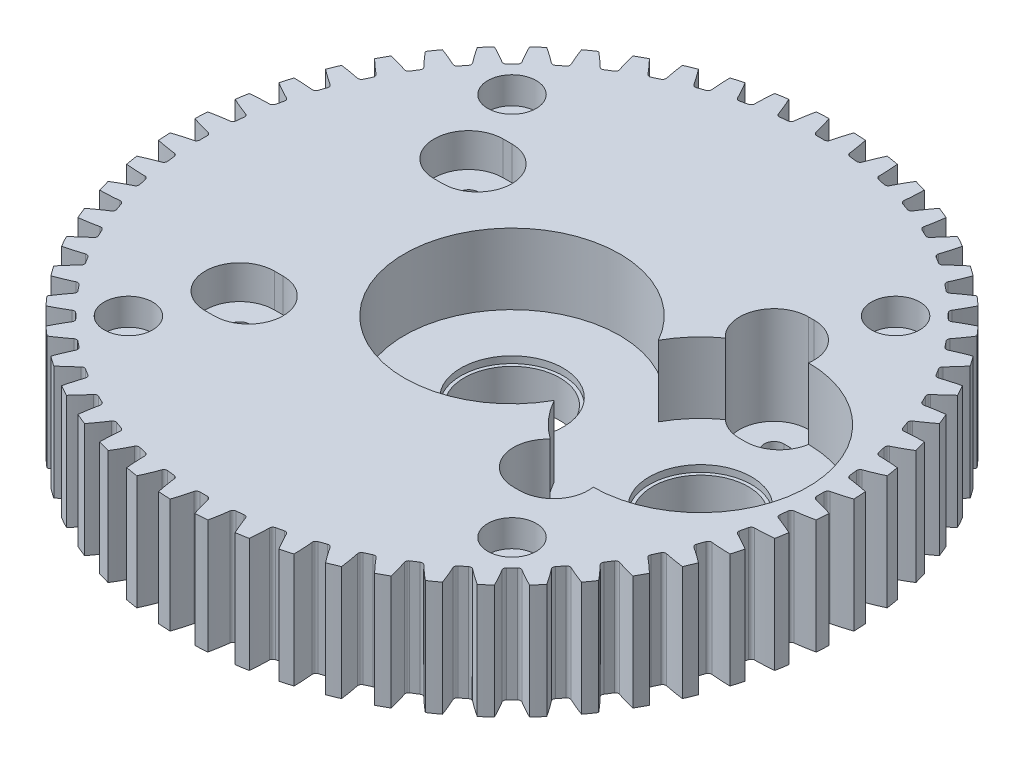
SolidWorks part; units mm, degrees
note: The reader was unsure of these and kept them because the rebuilt part matched: shared geometry of "Sketch10<3>".
ref_plane "Front Plane" through (0, 0, 0) normal (0, 0, 1) x (1, 0, 0)
ref_plane "Top Plane" through (0, 0, 0) normal (0, 1, 0) x (1, 0, 0)
ref_plane "Right Plane" through (0, 0, 0) normal (1, 0, 0) x (0, 0, -1)
sketch "Sketch1" plane through (0, 0, 0) normal (0, 1, 0) x (1, 0, 0)
  line L1 (-28.5, 28.5) -> (28.5, 28.5) construction
  line L2 (-28.5, 28.5) -> (-28.5, -28.5) construction
  line L3 (-28.5, -28.5) -> (28.5, -28.5) construction
  line L4 (28.5, 28.5) -> (28.5, -28.5) construction
  line L5 (-28.5, 28.5) -> (28.5, -28.5) construction
  line L6 (-28.5, -28.5) -> (28.5, 28.5) construction
  circle A0 centre (0, 0) radius 49
  circle A1 centre (-28.5, 28.5) radius 2.1
  circle A2 centre (28.5, 28.5) radius 2.1
  circle A3 centre (28.5, -28.5) radius 2.1
  circle A4 centre (-28.5, -28.5) radius 2.1
  dimension "D1" = 98
  dimension "D3" = 4.2
  dimension "D2" = 57
extrude "Boss-Extrude1" add sketch "Sketch1" along normal blind 17
sketch "Sketch5" plane through (0, 17, 0) normal (0, 1, 0) x (1, 0, 0)
  line L0 (0, 0) -> (0, 59.2156) construction
  line L2 (-0.5598, 45.8381) -> (0.5598, 45.8381)
  line L3 (0.5598, 46.3381) -> (0.5598, 45.8381)
  arc A1 (1.0455, 46.2191) -> (1.8387, 48.9655) centre (35.0396, 37.8887) cw
  circle A6 centre (0, 0) radius 48
  circle A7 centre (0, 0) radius 45.8381
  arc A10 (-1.0455, 46.2191) -> (-1.8387, 48.9655) centre (-35.0396, 37.8887) ccw
  arc A11 (-1.8387, 48.9655) -> (1.8387, 48.9655) centre (0, 45.6487) cw
  arc A12 (-1.0455, 46.2191) -> (-0.5598, 45.8381) centre (-0.5598, 46.3381) ccw
  arc A13 (1.0455, 46.2191) -> (0.5598, 45.8381) centre (0.5598, 46.3381) cw
  circle A14 centre (0, 0) radius 49 construction
  point P6 (0, 45.8381)
  point P9 (0.5, 48)
  point P14 (0, 48)
  dimension "D3" = 0.5598
  dimension "D1" = 91.6763
  dimension "D2" = 96
  dimension "D4" = 35
  dimension "D5" = 0.5
  dimension "D6" = 0.5
  dimension "D7" = 1.8387
  dimension "D8" = 1.0455
extrude "Cut-Extrude1" cut sketch "Sketch5" against normal through all
pattern_circular "CirPattern1" count 56 over 360 about axis through (0, 0, 0) along (0, 1, 0) of "Cut-Extrude1"
sketch "Sketch6" plane through (0, 17, 0) normal (0, 1, 0) x (1, 0, 0)
  line L0 (0, 0) -> (28, 0)
  circle A0 centre (0, 0) radius 16
  circle A1 centre (28, 0) radius 16
  dimension "D2" = 32
  dimension "D3" = 32
  dimension "D1" = 28
extrude "Cut-Extrude2" cut sketch "Sketch6" against normal blind 10.5
sketch "Sketch7" plane through (0, 17, 0) normal (0, 1, 0) x (1, 0, 0)
  line L0 (0, 0) -> (28, 0)
  circle A0 centre (0, 0) radius 7.1
  circle A1 centre (28, 0) radius 7.1
  dimension "D1" = 14.2
  dimension "D3" = 14.2
  dimension "D2" = 28
extrude "Cut-Extrude3" cut sketch "Sketch7" against normal through all
sketch "Sketch8" plane through (0, 17, 0) normal (0, 1, 0) x (1, 0, 0)
  circle A0 centre (0, 0) radius 7.6
  circle A1 centre (28, 0) radius 7.6
  dimension "D1" = 15.2
  dimension "D2" = 15.2
extrude "Cut-Extrude4" cut sketch "Sketch8" against normal blind 11.5
sketch "Sketch9" plane through (0, 17, 0) normal (0, 1, 0) x (1, 0, 0)
  line L1 (-28, 0) -> (28, 0) construction
  line L3 (23, -16.785) -> (22.15, -16.785)
  line L6 (28, -16.785) -> (23, -16.785) construction
  line L7 (22.15, -18.235) -> (23, -18.235)
  line L10 (28, 0) -> (28, -16.785) construction
  line L11 (22.15, -15.335) -> (23, -15.335)
  line L13 (22.15, -18.235) -> (23, -18.235)
  line L14 (22.15, -15.335) -> (23, -15.335)
  line L15 (22.15, -18.235) -> (23, -18.235)
  line L16 (22.15, -15.335) -> (23, -15.335)
  line L17 (22.15, -18.235) -> (23, -18.235)
  line L18 (22.15, -15.335) -> (23, -15.335)
  line L19 (28, 16.785) -> (23, 16.785) construction
  line L20 (22.15, 15.335) -> (23, 15.335)
  line L21 (22.15, 18.235) -> (23, 18.235)
  line L22 (22.15, 15.335) -> (23, 15.335)
  line L23 (22.15, 18.235) -> (23, 18.235)
  line L24 (22.15, 15.335) -> (23, 15.335)
  line L25 (22.15, 18.235) -> (23, 18.235)
  line L26 (22.15, 15.335) -> (23, 15.335)
  line L27 (22.15, 18.235) -> (23, 18.235)
  line L28 (0, 0) -> (0, -29.297) construction
  line L29 (-22.15, -15.55) -> (-23.45, -15.55)
  line L30 (-22.15, -18.45) -> (-23.45, -18.45)
  line L31 (-28, -17) -> (-23.45, -17) construction
  line L32 (-22.15, -15.55) -> (-23.45, -15.55)
  line L33 (-22.15, -18.45) -> (-23.45, -18.45)
  line L34 (-22.15, -15.55) -> (-23.45, -15.55)
  line L35 (-22.15, -18.45) -> (-23.45, -18.45)
  line L36 (-22.15, -15.55) -> (-23.45, -15.55)
  line L37 (-22.15, -18.45) -> (-23.45, -18.45)
  line L40 (-22.15, -15.55) -> (-23.45, -15.55)
  line L41 (-22.15, -18.45) -> (-23.45, -18.45)
  line L42 (-22.15, -15.55) -> (-23.45, -15.55)
  line L43 (-22.15, -18.45) -> (-23.45, -18.45)
  line L44 (-22.15, -15.55) -> (-23.45, -15.55)
  line L45 (-22.15, -18.45) -> (-23.45, -18.45)
  line L46 (-22.15, -15.55) -> (-23.45, -15.55)
  line L47 (-22.15, -18.45) -> (-23.45, -18.45)
  line L48 (-23.45, -17) -> (-22.15, -17)
  line L49 (-28, 17) -> (-23.45, 17) construction
  line L50 (-23.45, 17) -> (-22.15, 17)
  line L51 (-22.15, 18.45) -> (-23.45, 18.45)
  line L52 (-22.15, 15.55) -> (-23.45, 15.55)
  line L53 (-22.15, 18.45) -> (-23.45, 18.45)
  line L54 (-22.15, 15.55) -> (-23.45, 15.55)
  line L55 (-22.15, 18.45) -> (-23.45, 18.45)
  line L56 (-22.15, 15.55) -> (-23.45, 15.55)
  line L57 (-22.15, 18.45) -> (-23.45, 18.45)
  line L58 (-22.15, 15.55) -> (-23.45, 15.55)
  line L59 (-22.15, 18.45) -> (-23.45, 18.45)
  line L60 (-22.15, 15.55) -> (-23.45, 15.55)
  line L61 (-22.15, 18.45) -> (-23.45, 18.45)
  line L62 (-22.15, 15.55) -> (-23.45, 15.55)
  line L63 (-22.15, 18.45) -> (-23.45, 18.45)
  line L64 (-22.15, 15.55) -> (-23.45, 15.55)
  line L65 (-22.15, 18.45) -> (-23.45, 18.45)
  line L66 (-22.15, 15.55) -> (-23.45, 15.55)
  arc A8 (23, -18.235) -> (23, -15.335) centre (23, -16.785) ccw
  arc A9 (22.15, -15.335) -> (22.15, -18.235) centre (22.15, -16.785) ccw
  arc A10 (22.15, 15.335) -> (22.15, 18.235) centre (22.15, 16.785) cw
  arc A11 (23, 18.235) -> (23, 15.335) centre (23, 16.785) cw
  arc A14 (-22.15, -15.55) -> (-22.15, -18.45) centre (-22.15, -17) cw
  arc A15 (-23.45, -18.45) -> (-23.45, -15.55) centre (-23.45, -17) cw
  arc A16 (-23.45, 18.45) -> (-23.45, 15.55) centre (-23.45, 17) ccw
  arc A17 (-22.15, 15.55) -> (-22.15, 18.45) centre (-22.15, 17) ccw
  point P5 (28, 0)
  point P30 (0, 0)
  point P40 (-28, 0)
  point P43 (-28, 0)
  dimension "D2" = 2.9
  dimension "D4" = 2.9
  dimension "D6" = 1.45
  dimension "D1" = 5
  dimension "D3" = 5.85
  dimension "D5" = 1.3
  dimension "D7" = 28
extrude "Cut-Extrude5" cut sketch "Sketch9" against normal through all
sketch "Sketch10" plane through (0, 17, 0) normal (0, 1, 0) x (1, 0, 0)
  line L0 (22.15, -11.66) -> (23, -11.66)
  line L1 (22.15, -21.91) -> (23, -21.91)
  line L2 (0, 0) -> (28, 0) construction
  line L3 (22.15, 21.91) -> (23, 21.91)
  line L4 (22.15, 11.66) -> (23, 11.66)
  line L5 (-23.45, -11.875) -> (-22.15, -11.875)
  line L6 (-23.45, -22.125) -> (-22.15, -22.125)
  line L7 (-23.45, 22.125) -> (-22.15, 22.125)
  line L8 (-23.45, 11.875) -> (-22.15, 11.875)
  arc A2 (23, -21.91) -> (23, -11.66) centre (23, -16.785) ccw
  arc A3 (22.15, -11.66) -> (22.15, -21.91) centre (22.15, -16.785) ccw
  arc A4 (22.15, 11.66) -> (22.15, 21.91) centre (22.15, 16.785) cw
  arc A5 (23, 21.91) -> (23, 11.66) centre (23, 16.785) cw
  arc A6 (-23.45, -11.875) -> (-23.45, -22.125) centre (-23.45, -17) ccw
  arc A7 (-22.15, -22.125) -> (-22.15, -11.875) centre (-22.15, -17) ccw
  arc A8 (-22.15, 22.125) -> (-22.15, 11.875) centre (-22.15, 17) cw
  arc A9 (-23.45, 11.875) -> (-23.45, 22.125) centre (-23.45, 17) cw
  dimension "D1" = 10.25
  dimension "D2" = 10.25
  dimension "D3" = 10.25
extrude "Cut-Extrude6" cut sketch "Sketch10" against normal blind 14.5 contours A5 L3 A4 L4 | L0 A3 L1 A2
sketch "Sketch11" plane through (0, 17, 0) normal (0, 1, 0) x (1, 0, 0)
  circle A0 centre (-28.5, -28.5) radius 3.6
  circle A1 centre (-28.5, 28.5) radius 3.6
  circle A2 centre (28.5, 28.5) radius 3.6
  circle A3 centre (28.5, -28.5) radius 3.6
  dimension "D1" = 7.2
extrude "Cut-Extrude7" cut sketch "Sketch11" against normal blind 4
extrude "Cut-Extrude8" cut sketch "Sketch10<3>" against normal blind 5 contours A9 L8 A8 L7 | L6 A7 L5 A6
sketch "Sketch10<3>" plane through (0, 17, 0) normal (0, 1, 0) x (1, 0, 0) same geometry as "Sketch10"
sketch "Sketch12" plane through (0, 17, 0) normal (0, 1, 0) x (1, 0, 0)
  circle A0 centre (22.15, -16.785) radius 1.45
  circle A1 centre (28, 0) radius 7.6
  dimension "D1" = 5.85
